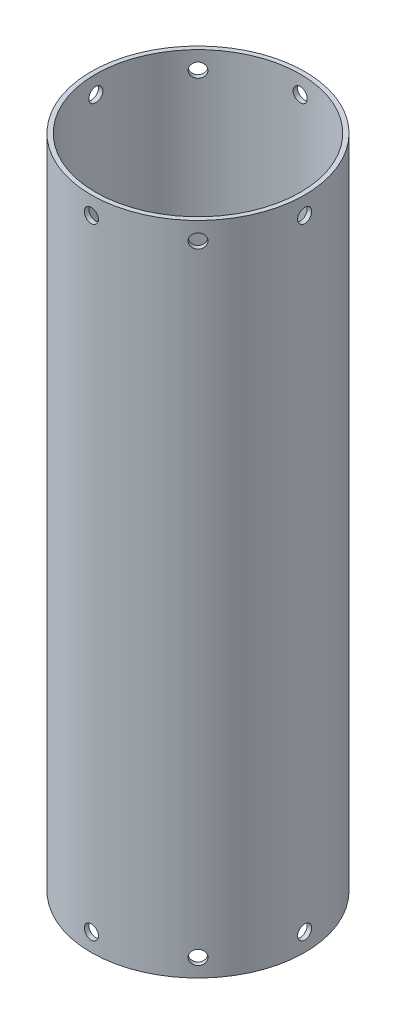
SolidWorks part; units mm, degrees
material "6061-T6 (SS)"
ref_plane "Front Plane" through (0, 0, 0) normal (0, 0, 1) x (1, 0, 0)
ref_plane "Top Plane" through (0, 0, 0) normal (0, 1, 0) x (1, 0, 0)
ref_plane "Right Plane" through (0, 0, 0) normal (1, 0, 0) x (0, 0, -1)
sketch "Sketch1" plane through (0, 0, 0) normal (0, 1, 0) x (1, 0, 0)
  circle A0 centre (0, 0) radius 76.2
  circle A1 centre (0, 0) radius 73.025
  dimension "D1" = 152.4
  dimension "D2" = 3.175
extrude "Boss-Extrude1" add sketch "Sketch1" along normal blind 467.995
sketch "Sketch2" [suppressed] plane through (0, 667.7406, 0) normal (1, 0, 0) x (0, 0, 1)
  circle A0 centre (0, -12.7) radius 4.7625 construction
  circle A1 centre (0, -12.7) radius 4.7625 construction
  circle A2 centre (0, -12.7) radius 5.0165
  dimension "D1" = 0.254
extrude "LOX Top Holes" [suppressed] cut sketch "Sketch2" along normal up to surface (76.0347 mm away) contours A2 up to face at (0, 467.995, 76.2)
pattern_circular "CirPattern1" [suppressed] count 8 over 360 of bodies 122
sketch "Sketch3" [suppressed] plane through (0, 25.4, 0) normal (1, 0, 0) x (0, 0, -1)
  circle A0 centre (0, -12.7) radius 4.7625 construction
  circle A1 centre (0, -12.7) radius 4.7625 construction
  circle A2 centre (0, -12.7) radius 5.0165
  dimension "D1" = 0.254
extrude "LOX Bottom Holes" [suppressed] cut sketch "Sketch3" along normal up to surface (76.0347 mm away) contours A2 up to face at (0, 467.995, 76.2)
pattern_circular "CirPattern2" [suppressed] count 8 over 360 of bodies 124
sketch "Sketch4" plane through (0, 442.595, 0) normal (1, 0, 0) x (0, 0, 1)
  circle A0 centre (0, -12.7) radius 4.7625 construction
  circle A1 centre (0, -12.7) radius 4.7625 construction
  circle A2 centre (0, -12.7) radius 5.0165
  dimension "D1" = 0.254
extrude "Cut-Extrude1" cut sketch "Sketch4" along normal up to surface (76.0347 mm away) contours A2 region at (0, 455.295, 0) up to face at (0, 467.995, 76.2)
pattern_circular "CirPattern3" count 8 over 360 about axis through (0, 467.995, 0) along (0, 1, 0) of "Cut-Extrude1"
sketch "Sketch7" plane through (0, 25.4, 0) normal (1, 0, 0) x (0, 0, -1)
  circle A0 centre (0, -12.7) radius 4.7625 construction
  circle A1 centre (0, -12.7) radius 4.7625 construction
  circle A2 centre (0, -12.7) radius 5.0165
  dimension "D1" = 0.254
extrude "Cut-Extrude2" cut sketch "Sketch7" along normal up to surface (76.0347 mm away) up to face at (0, 467.995, 76.2)
pattern_circular "CirPattern4" count 8 over 360 about axis through (0, 0, 0) along (0, 1, 0) of "Cut-Extrude2"
